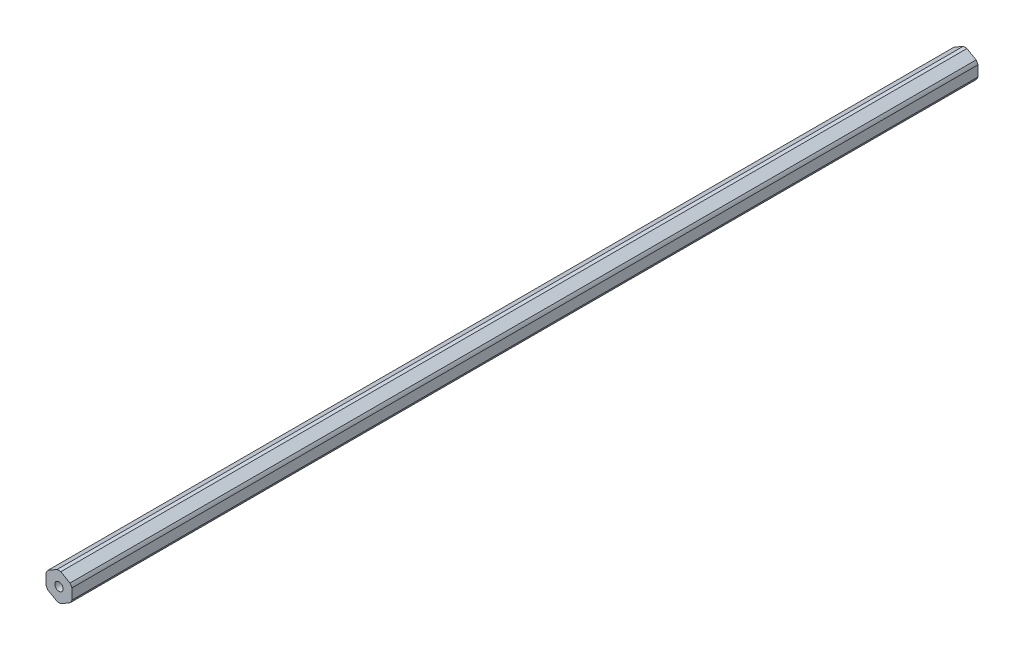
SolidWorks part; units mm, degrees
ref_plane "Front Plane" through (0, 0, 0) normal (0, 0, 1) x (1, 0, 0)
ref_plane "Top Plane" through (0, 0, 0) normal (0, 1, 0) x (1, 0, 0)
ref_plane "Right Plane" through (0, 0, 0) normal (1, 0, 0) x (0, 0, -1)
sketch "Sketch1" plane through (0, 0, 0) normal (0, 0, 1) x (1, 0, 0)
  line L1 (6.35, 3.6662) -> (0, 7.3323)
  line L2 (0, 7.3323) -> (-6.35, 3.6662)
  line L3 (-6.35, 3.6662) -> (-6.35, -3.6662)
  line L4 (-6.35, -3.6662) -> (0, -7.3323)
  line L5 (0, -7.3323) -> (6.35, -3.6662)
  line L6 (6.35, -3.6662) -> (6.35, 3.6662)
  circle A0 centre (0, 0) radius 6.35 construction
  circle A1 centre (0, 0) radius 6.858
  dimension "D1" = 12.7
  dimension "D2" = 13.716
extrude "Boss-Extrude1" add sketch "Sketch1" along normal mid plane 444.5 contours L6 A1 L1 L2 L3 L4 L5 region at (0, 0, 0)
hole_wizard "#10-32 Tapped Hole1" positions "3DSketch1" profile "Sketch2" tap size "#10-32" standard "ANSI Inch"
sketch3d "3DSketch1"
  line L0 (0, 0, 222.25) -> (0, 0, -222.25) construction
  point P0 (0, 0, 222.25)
  point P4 (0, 0, -222.25)
sketch "Sketch2" plane through (0, 0, 222.25) normal (1, 0, 0) x (0, -1, 0)
  line L0 (0, 0) -> (0, 16.2908)
  line L1 (0, 16.2908) -> (2.0193, 15.0774)
  line L2 (2.0193, 15.0774) -> (2.0193, 0)
  line L5 (2.0193, 0) -> (0, 0)
  line L10 (0, 16.2908) -> (-2.0193, 15.0774) construction
  line L11 (0, -6.35) -> (0, 107.95) construction
  dimension "Tap Drill Dia." = 4.0386
  dimension "Tap Drill Depth" = 15.0774
  dimension "Drill Angle" = 118
cosmetic thread "Hole Thread1" parameters "D1"=12.7, "D2"=4.826
cosmetic thread "Hole Thread2" parameters "D1"=12.7, "D2"=4.826
